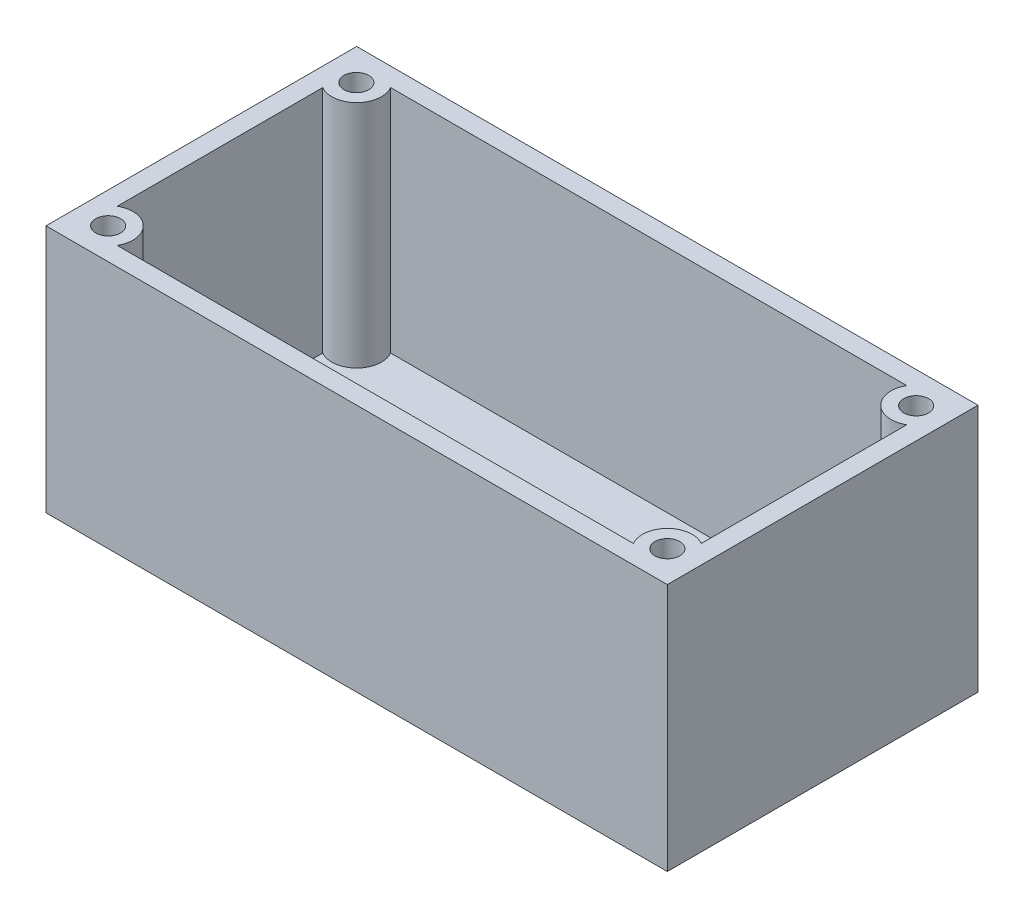
SolidWorks part; units mm, degrees
ref_plane "前视基准面" through (0, 0, 0) normal (0, 0, 1) x (1, 0, 0)
ref_plane "上视基准面" through (0, 0, 0) normal (0, 1, 0) x (1, 0, 0)
ref_plane "右视基准面" through (0, 0, 0) normal (1, 0, 0) x (0, 0, -1)
sketch "草图1" plane through (0, 0, 0) normal (0, 1, 0) x (1, 0, 0)
  line L1 (0, 0) -> (50, 0)
  line L2 (0, 0) -> (0, 25)
  line L3 (0, 25) -> (50, 25)
  line L4 (50, 0) -> (50, 25)
  circle A0 centre (2.5, 22.5) radius 2
  circle A1 centre (47.5, 22.5) radius 2
  circle A2 centre (47.5, 2.5) radius 2
  circle A3 centre (2.5, 2.5) radius 2
  dimension "D3" = 4
  dimension "D1" = 50
  dimension "D2" = 25
  dimension "D4" = 2.5
  dimension "D5" = 2.5
  dimension "D6" = 2
  dimension "D7" = 2
extrude "凸台-拉伸3" add sketch "草图1" along normal blind 20 contours L1 L4 L3 L2 A3 A2 A1 A0 | A0 | A1 | A2 | A3 region at (25, 0, -12.5) region at (2.5, 0, -22.5) region at (47.5, 0, -22.5) region at (47.5, 0, -2.5) region at (2.5, 0, -2.5)
shell "抽壳1" thickness 1.5 removed face at (25, 20, -12.5)
extrude "凸台-拉伸4" add sketch "草图1<3>" along normal blind 20 contours A0 | A1 | A2 | A3 region at (2.5, 0, -22.5) region at (47.5, 0, -22.5) region at (47.5, 0, -2.5) region at (2.5, 0, -2.5)
sketch "草图1<3>" plane through (0, 0, 0) normal (0, 1, 0) x (1, 0, 0) same geometry as "草图1"
hole_wizard "M2x0.4 螺纹孔3" positions "草图8" profile "草图9" tap size "M2x0.4" standard "ANSI Metric"
sketch "草图8" plane through (0, 20, 0) normal (0, 1, 0) x (1, 0, 0)
  point P0 (47.5533, 22.4718)
  point P2 (47.5, 2.5)
  point P5 (2.5036, 22.4718)
  point P7 (2.5, 2.5)
sketch "草图9" plane through (47.5533, 20, -22.4718) normal (1, 0, 0) x (0, 0, 1)
  line L0 (0, 0) -> (0, 8.4807)
  line L1 (0, 8.4807) -> (0.8, 8)
  line L2 (0.8, 8) -> (0.8, 4)
  line L3 (0.8, 4) -> (1, 4)
  line L4 (1, 4) -> (1, 0)
  line L5 (1, 0) -> (0, 0)
  line L10 (0, 8.4807) -> (-0.8, 8) construction
  line L11 (0, -6.35) -> (0, 107.95) construction
  dimension "螺纹孔钻头直径" = 1.6
  dimension "螺纹孔钻头深度" = 8
  dimension "螺纹主直径" = 2
  dimension "螺纹深度" = 4
  dimension "导头角度" = 118
